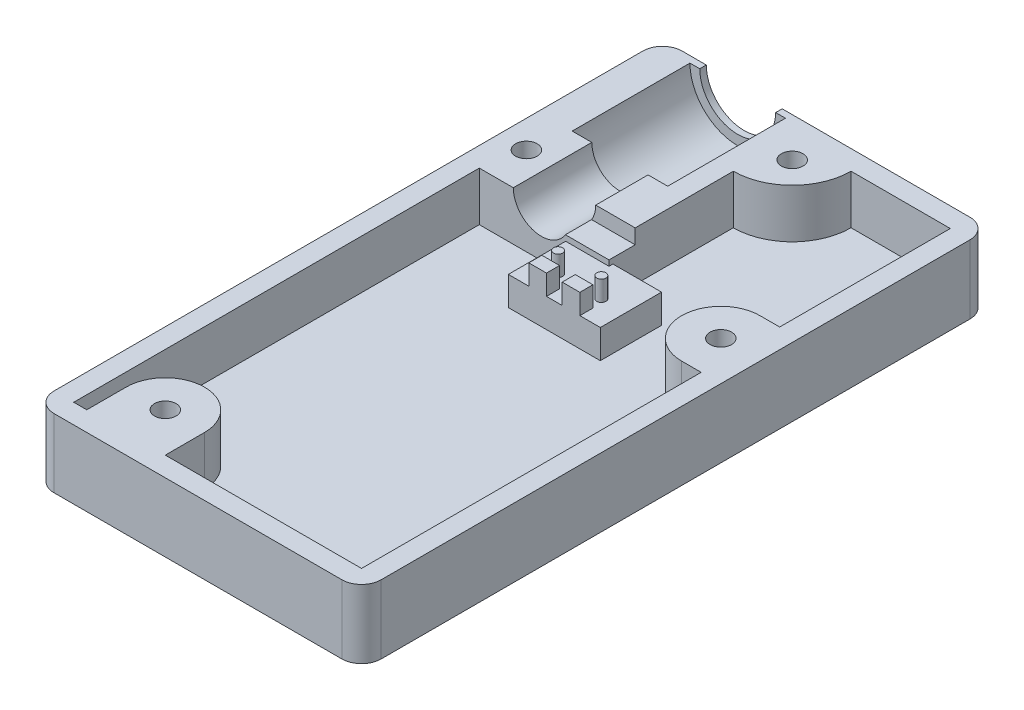
SolidWorks part; units mm, degrees
ref_plane "前视基准面" through (0, 0, 0) normal (0, 0, 1) x (1, 0, 0)
ref_plane "上视基准面" through (0, 0, 0) normal (0, 1, 0) x (1, 0, 0)
ref_plane "右视基准面" through (0, 0, 0) normal (1, 0, 0) x (0, 0, -1)
sketch "草图1" plane through (0, 0, 0) normal (0, 0, 1) x (1, 0, 0)
  line L1 (50, 38) -> (0, 38)
  line L2 (50, 38) -> (50, 0)
  line L3 (50, 0) -> (0, 0)
  line L4 (0, 38) -> (0, 0)
  dimension "D1" = 50
  dimension "D2" = 38
extrude "凸台-拉伸1" add sketch "草图1" against normal blind 3
sketch "草图2" plane through (0, 0, 0) normal (0, 0, 1) x (1, 0, 0)
  line L8 (50, 0) -> (50, 38)
  line L9 (50, 38) -> (0, 38)
  line L10 (0, 38) -> (0, 0)
  line L11 (0, 0) -> (50, 0)
  line L12 (50, 0) -> (50, 38)
  line L13 (50, 38) -> (0, 38)
  line L14 (0, 38) -> (0, 0)
  line L15 (0, 0) -> (50, 0)
  line L20 (47, 3) -> (47, 35)
  line L21 (47, 35) -> (3, 35)
  line L22 (3, 35) -> (3, 3)
  line L23 (3, 3) -> (47, 3)
  line L24 (47, 3) -> (47, 35)
  line L25 (47, 35) -> (3, 35)
  line L26 (3, 35) -> (3, 3)
  line L27 (3, 3) -> (47, 3)
  dimension "D1" = 0
  dimension "D2" = 3
extrude "凸台-拉伸2" add sketch "草图2" along normal blind 90
sketch "草图4" plane through (0, 0, -3) normal (0, 0, -1) x (-1, 0, 0)
  line L0 (-50, 38) -> (0, 38) construction
  line L1 (0, 38) -> (0, 0) construction
  circle A0 centre (-12.5, 10.5) radius 7.3
  dimension "D1" = 14.6
  dimension "D3" = 12.5
  dimension "D2" = 27.5
extrude "切除-拉伸1" cut sketch "草图4" against normal blind 45.2
sketch "草图5" plane through (0, 0, 0) normal (0, 0, 1) x (1, 0, 0)
  circle A0 centre (12.5, 10.5) radius 7.3
  circle A1 centre (12.5, 10.5) radius 7.3 construction
  circle A2 centre (12.5, 10.5) radius 10.3
  dimension "D1" = 3
extrude "凸台-拉伸3" add sketch "草图5" along normal blind 16
sketch "草图6" plane through (0, 0, -3) normal (0, 0, -1) x (-1, 0, 0)
  circle A0 centre (-12.5, 10.5) radius 5.8
  circle A3 centre (-12.5, 10.5) radius 7.3 construction
  circle A4 centre (-12.5, 10.5) radius 8.3
  circle A5 centre (-12.5, 10.5) radius 8.3
  dimension "D1" = 1
  dimension "D2" = 1.5
extrude "凸台-拉伸5" add sketch "草图6" against normal blind 1
sketch "草图7" plane through (0, 0, 16) normal (0, 0, 1) x (1, 0, 0)
  line L2 (5.4403, 3) -> (19.5597, 3)
  line L4 (5.4403, 3) -> (19.5597, 3)
  line L5 (3, 14.4799) -> (3, 6.5201)
  line L8 (3, 14.4799) -> (3, 6.5201)
  arc A1 (3, 6.5201) -> (5.4403, 3) centre (12.5, 10.5) ccw
  arc A2 (3, 6.5201) -> (5.4403, 3) centre (12.5, 10.5) ccw
  circle A3 centre (12.5, 10.5) radius 4.3
  arc A10 (19.5597, 3) -> (3, 14.4799) centre (12.5, 10.5) ccw
  arc A11 (19.5597, 3) -> (3, 14.4799) centre (12.5, 10.5) ccw
  dimension "D2" = 8.6
  dimension "D1" = 0
extrude "凸台-拉伸6" add sketch "草图7" along normal blind 2
sketch "草图8" plane through (0, 0, 18) normal (0, 0, 1) x (1, 0, 0)
  circle A1 centre (12.5, 10.5) radius 6.3
  circle A2 centre (12.5, 10.5) radius 4.3
  circle A3 centre (12.5, 10.5) radius 4.3
  dimension "D1" = 0
  dimension "D2" = 2
extrude "凸台-拉伸7" add sketch "草图8" along normal blind 10
sketch "草图9" plane through (0, 0, 28) normal (0, 0, 1) x (1, 0, 0)
  line L0 (8.2, 10.5) -> (16.8, 10.5) construction
  line L2 (16.1644, 8.25) -> (18.8, 8.25)
  line L3 (16.1644, 8.25) -> (16.1644, 12.75)
  line L4 (16.1644, 12.75) -> (18.8, 12.75)
  line L5 (18.8, 8.25) -> (18.8, 12.75)
  circle A0 centre (12.5, 10.5) radius 4.3 construction
  circle A1 centre (12.5, 10.5) radius 6.3 construction
  dimension "D1" = 4.5
extrude "切除-拉伸2" cut sketch "草图9" against normal blind 4
sketch "草图10" plane through (0, 3, 0) normal (0, 1, 0) x (1, 0, 0)
  line L0 (19.33, -36.76) -> (19.33, -34.76)
  line L1 (19.33, -34.76) -> (22.03, -34.76)
  line L2 (22.03, -34.76) -> (22.03, -36.76)
  line L3 (22.03, -36.76) -> (19.33, -36.76)
  line L8 (23.23, -37.46) -> (23.23, -28) construction
  line L9 (23.43, -37.46) -> (23.03, -37.46) construction
  line L10 (16.8, -28) -> (29.66, -28) construction
  line L11 (27.13, -34.76) -> (24.43, -34.76)
  line L12 (24.43, -34.76) -> (24.43, -36.76)
  line L13 (24.43, -36.76) -> (27.13, -36.76)
  line L14 (27.13, -36.76) -> (27.13, -34.76)
  line L15 (18.53, -37.26) -> (18.53, -34.14) construction
  line L16 (22.83, -37.26) -> (22.83, -34.14) construction
  line L17 (20.92, -34.36) -> (18.92, -34.36) construction
  circle A0 centre (19.92, -32.88) radius 0.7
  circle A1 centre (26.54, -32.88) radius 0.7
  circle A2 centre (19.92, -32.88) radius 0.98 construction
  point P14 (18.53, -35.7)
  dimension "D1" = 1.4
  dimension "D2" = 0.28
  dimension "D3" = 0.8
  dimension "D4" = 0.8
  dimension "D5" = 0.4
  dimension "D6" = 2
extrude "凸台-拉伸8" add sketch "草图10" along normal blind 32
sketch "草图11" plane through (0, 3, 0) normal (0, 1, 0) x (1, 0, 0)
  line L0 (16.8, -34.14) -> (16.8, -28) construction
  line L1 (16.2, -36.76) -> (30.26, -36.76)
  line L2 (16.2, -36.76) -> (16.2, -27.4)
  line L3 (16.2, -27.4) -> (30.26, -27.4)
  line L4 (30.26, -36.76) -> (30.26, -27.4)
  line L5 (29.66, -28) -> (29.66, -34.14) construction
  line L6 (19.33, -36.76) -> (22.03, -36.76) construction
  line L7 (16.8, -28) -> (29.66, -28) construction
  dimension "D1" = 0.6
  dimension "D2" = 0.6
  dimension "D3" = 0.6
extrude "凸台-拉伸9" add sketch "草图11" along normal blind 4.4
sketch "草图12" plane through (0, 35, 0) normal (0, -1, 0) x (1, 0, 0)
  line L1 (16.2, 27.4) -> (30.26, 27.4)
  line L2 (16.2, 27.4) -> (16.2, 36.76)
  line L3 (16.2, 36.76) -> (30.26, 36.76)
  line L4 (30.26, 27.4) -> (30.26, 36.76)
extrude "凸台-拉伸10" add sketch "草图12" along normal blind 21.2
sketch "草图13" plane through (0, 38, 0) normal (0, 1, 0) x (1, 0, 0)
  line L0 (12.3, -64.096) -> (42.5, -64.096) construction
  line L1 (40.04, -72.896) -> (39.0237, -72.896) construction
  line L2 (38.625, -74.196) -> (44.4, -74.196)
  line L3 (45.4, -73.196) -> (45.4, -54.996)
  line L4 (44.4, -57.796) -> (44.4, -70.396) construction
  line L5 (38.625, -53.996) -> (44.4, -53.996)
  circle A0 centre (27.4, -64.096) radius 15.1 construction
  circle A1 centre (27.4, -64.096) radius 14.1 construction
  arc A2 (38.625, -74.196) -> (38.625, -53.996) centre (27.4, -64.096) cw
  arc A3 (44.4, -53.996) -> (45.4, -54.996) centre (44.4, -54.996) cw
  arc A4 (44.4, -74.196) -> (45.4, -73.196) centre (44.4, -73.196) ccw
  point P16 (45.4, -64.096)
  point P18 (45.4, -53.996)
  point P21 (45.4, -74.196)
  dimension "D1" = 1
  dimension "D2" = 1.3
  dimension "D4" = 1
  dimension "D3" = 1
extrude "切除-拉伸3" cut sketch "草图13" against normal blind 3
sketch "草图14" plane through (0, 35, 0) normal (0, -1, 0) x (1, 0, 0)
  line L0 (14.3, 64.096) -> (40.5, 64.096) construction
  line L1 (23.9, 46.596) -> (23.9, 50.4373) construction
  line L2 (30.9, 46.596) -> (30.9, 50.4373) construction
  line L3 (23.9, 46.596) -> (23.9, 49.4072)
  line L4 (30.9, 46.596) -> (30.9, 49.4072)
  line L5 (30.9, 81.596) -> (30.9, 78.7847)
  line L6 (23.9, 81.596) -> (23.9, 78.7847)
  circle A0 centre (27.4, 46.596) radius 1.65
  circle A1 centre (27.4, 64.096) radius 13.1 construction
  arc A2 (23.9, 49.4072) -> (30.9, 49.4072) centre (27.4, 64.096) ccw
  arc A3 (38.625, 74.196) -> (38.625, 53.996) centre (27.4, 64.096) ccw construction
  arc A4 (23.9, 46.596) -> (30.9, 46.596) centre (27.4, 46.596) ccw
  arc A5 (23.9, 46.596) -> (30.9, 46.596) centre (27.4, 46.596) ccw construction
  arc A6 (23.9, 81.596) -> (30.9, 81.596) centre (27.4, 81.596) cw
  arc A7 (23.9, 78.7847) -> (30.9, 78.7847) centre (27.4, 64.096) cw
  circle A8 centre (27.4, 81.596) radius 1.65
  dimension "D1" = 3.3
extrude "凸台-拉伸11" add sketch "草图14" along normal blind 15.5
sketch "草图15" plane through (0, 35, 0) normal (0, -1, 0) x (1, 0, 0)
  line L0 (23.9, 46.596) -> (23.9, 50.4373) construction
  line L1 (20.4, 50.7165) -> (20.4, 46.596)
  line L2 (27.4, 48.696) -> (27.4, 44.496) construction
  line L4 (34.4, 50.7165) -> (34.4, 46.596)
  line L5 (45.4, 64.096) -> (12.3, 64.096) construction
  line L6 (45.4, 73.196) -> (45.4, 54.996) construction
  line L7 (20.4, 77.4754) -> (20.4, 81.596)
  line L8 (34.4, 77.4754) -> (34.4, 81.596)
  circle A0 centre (27.4, 46.596) radius 1.65
  circle A1 centre (27.4, 46.596) radius 2.1 construction
  arc A2 (20.4, 46.596) -> (34.4, 46.596) centre (27.4, 46.596) ccw
  arc A3 (20.4, 50.7165) -> (34.4, 50.7165) centre (27.4, 64.096) ccw
  arc A4 (23.9, 78.7847) -> (23.9, 49.4072) centre (27.4, 64.096) ccw construction
  arc A5 (20.4, 77.4754) -> (34.4, 77.4754) centre (27.4, 64.096) cw
  circle A6 centre (27.4, 81.596) radius 1.65
  arc A7 (20.4, 81.596) -> (34.4, 81.596) centre (27.4, 81.596) cw
  arc A9 (30.9, 49.4072) -> (38.625, 53.996) centre (27.4, 64.096) ccw construction
  line M14 (23.9, 78.7847) -> (23.9, 81.596)
  arc M15 (23.9, 81.596) -> (30.9, 81.596) centre (27.4, 81.596) cw
  line M16 (30.9, 81.596) -> (30.9, 78.7847)
  line M24 (30.9, 49.4072) -> (30.9, 46.596)
  arc M25 (30.9, 46.596) -> (23.9, 46.596) centre (27.4, 46.596) cw
  line M26 (23.9, 46.596) -> (23.9, 49.4072)
  dimension "D1" = 3.3
  dimension "D2" = 7
extrude "凸台-拉伸12" add sketch "草图15" along normal blind 15.5 contours L1 A2 L4 M24 M25 M26 | A7 L7 L8 M14 M15 M16 region at (22.0467, 35, 49.7857) region at (20.5788, 35, 79.5357)
sketch "草图16" plane through (0, 19.5, 0) normal (0, -1, 0) x (1, 0, 0)
  line L0 (45.4, 64.096) -> (12.3, 64.096) construction
  line L1 (45.4, 73.196) -> (45.4, 54.996) construction
  line L24 (31.3, 81.596) -> (31.3, 77.2291)
  line L25 (23.5, 77.2291) -> (23.5, 81.596)
  line L26 (31.3, 46.596) -> (31.3, 50.9628)
  line L27 (23.5, 50.9628) -> (23.5, 46.596)
  line L28 (31.3, 46.596) -> (31.3, 50.9628)
  line L29 (23.5, 50.9628) -> (23.5, 46.596)
  arc A0 (20.4, 77.4754) -> (20.4, 50.7165) centre (27.4, 64.096) ccw construction
  arc A25 (23.5, 81.596) -> (31.3, 81.596) centre (27.4, 81.596) cw
  arc A26 (23.5, 77.2291) -> (31.3, 77.2291) centre (27.4, 64.096) cw
  arc A27 (23.5, 50.9628) -> (31.3, 50.9628) centre (27.4, 64.096) ccw
  arc A28 (23.5, 46.596) -> (31.3, 46.596) centre (27.4, 46.596) ccw
  arc A29 (23.5, 50.9628) -> (31.3, 50.9628) centre (27.4, 64.096) ccw
  arc A30 (23.5, 46.596) -> (31.3, 46.596) centre (27.4, 46.596) ccw
  dimension "D1" = 0.4
extrude "切除-拉伸4" cut sketch "草图16" against normal blind 0.8
sketch "草图17" plane through (0, 0, 0) normal (0, 0, 1) x (1, 0, 0)
  line L1 (3, 3) -> (47, 3) construction
  line L2 (22.83, 10.5392) -> (22.83, 3)
  line L3 (22.83, 10.2892) -> (22.83, 10.7892) construction
  line L4 (22.83, 3) -> (19.5597, 3)
  line L5 (5.4403, 3) -> (3, 3)
  line L6 (3, 3) -> (3, 6.5201)
  line L7 (3, 14.4799) -> (3, 35)
  line L8 (3, 35) -> (22.83, 35)
  line L9 (47, 35) -> (3, 35) construction
  line L10 (22.83, 10.5392) -> (22.83, 35)
  arc A1 (5.4403, 3) -> (3, 6.5201) centre (12.5, 10.5) cw
  arc A2 (3, 6.5201) -> (5.4403, 3) centre (12.5, 10.5) ccw construction
  arc A3 (3, 14.4799) -> (19.5597, 3) centre (12.5, 10.5) cw
  arc M1 (3, 14.4799) -> (19.5597, 3) centre (12.5, 10.5) cw
  line M2 (19.5597, 3) -> (47, 3)
  line M4 (47, 35) -> (3, 35)
  line M5 (3, 35) -> (3, 14.4799)
extrude "凸台-拉伸13" add sketch "草图17" along normal blind 18 contours L2 L10 M4 M5 M1 M2 | L5 A1 L6 region at (13.2696, 26.2496, 0) region at (3.7547, 4.0789, 0)
sketch "草图18" plane through (0, 0, 18) normal (0, 0, 1) x (1, 0, 0)
  line L8 (3, 35) -> (3, 3)
  line L9 (3, 3) -> (22.83, 3)
  line L10 (22.83, 3) -> (22.83, 35)
  line L11 (22.83, 35) -> (3, 35)
  line L12 (3, 35) -> (3, 3)
  line L13 (3, 3) -> (22.83, 3)
  line L14 (22.83, 3) -> (22.83, 35)
  line L15 (22.83, 35) -> (3, 35)
  circle A0 centre (12.5, 10.5) radius 6.3
  circle A1 centre (12.5, 10.5) radius 6.3 construction
  dimension "D1" = 0
extrude "凸台-拉伸14" add sketch "草图18" along normal blind 10
sketch "草图19" plane through (0, 0, 28) normal (0, 0, 1) x (1, 0, 0)
  line L0 (18.3845, 8.25) -> (22.83, 8.25)
  line L1 (22.83, 7.4) -> (22.83, 13.8) construction
  line L2 (22.83, 8.25) -> (22.83, 12.75)
  line L3 (22.83, 12.75) -> (18.3845, 12.75)
  line L4 (18.3845, 12.75) -> (16.1644, 12.75) construction
  line L5 (18.3845, 8.25) -> (18.3845, 12.75)
extrude "切除-拉伸5" cut sketch "草图19" against normal blind 4
sketch "草图23" plane through (0, 35, 0) normal (0, -1, 0) x (1, 0, 0)
  line L0 (22.83, 27.4) -> (22.83, 0) construction
  line L1 (22.83, 0) -> (47, 0) construction
  line L2 (22.83, 0) -> (22.83, 9)
  line L3 (22.83, 0) -> (31.83, 0)
  line L4 (47, 90) -> (47, 0) construction
  line L5 (44, 26.08) -> (47, 26.08)
  line L6 (47, 26.08) -> (47, 38.08)
  line L7 (45.65, 32.08) -> (42.35, 32.08) construction
  line L8 (44, 38.08) -> (47, 38.08)
  line L9 (30.26, 32.08) -> (42.35, 32.08) construction
  line L10 (30.26, 36.76) -> (30.26, 27.4) construction
  line L11 (3, 90) -> (3, 28) construction
  line L12 (0, 90) -> (50, 90) construction
  line L13 (11, 82.35) -> (11, 85.65) construction
  line L14 (5, 90) -> (5, 84)
  line L15 (17, 90) -> (17, 84)
  line L16 (5, 90) -> (17, 90)
  circle A0 centre (25.83, 3) radius 1.65
  arc A1 (31.83, 0) -> (22.83, 9) centre (22.83, 0) ccw
  circle A2 centre (44, 32.08) radius 1.65
  arc A3 (44, 26.08) -> (44, 38.08) centre (44, 32.08) cw
  circle A4 centre (11, 84) radius 1.65
  arc A5 (5, 84) -> (17, 84) centre (11, 84) ccw
  point P22 (47, 32.08)
  dimension "D1" = 3
  dimension "D4" = 3.3
  dimension "D5" = 3
  dimension "D6" = 3.3
  dimension "D7" = 6
  dimension "D8" = 3.3
  dimension "D9" = 8
  dimension "D10" = 6
  dimension "D11" = 6
  dimension "D2" = 3
  dimension "D3" = 9
extrude "凸台-拉伸16" add sketch "草图23" along normal through all
sketch "草图25" plane through (0, 35, 0) normal (0, -1, 0) x (1, 0, 0)
  line L0 (0, -3) -> (0, 90) construction
  line L1 (16.2, 28) -> (3, 28) construction
  circle A0 centre (4.2, 22) radius 1.65
  circle A1 centre (4.2, 22) radius 3 construction
  circle A2 centre (25.83, 3) radius 1.65
  circle A7 centre (44, 32.08) radius 1.65
  circle A8 centre (44, 32.08) radius 1.65
  circle A10 centre (11, 84) radius 1.65
  circle A11 centre (11, 84) radius 1.65
  dimension "D1" = 3.3
  dimension "D2" = 6
  dimension "D3" = 4.2
  dimension "D4" = 6
  dimension "D5" = 0
  dimension "D6" = 0
extrude "切除-拉伸7" cut sketch "草图25" against normal through all and the other way through all
sketch "草图26" plane through (0, 38, 0) normal (0, 1, 0) x (1, 0, 0)
  line L0 (0, 3) -> (0, -90) construction
  line L1 (4.2, -18.5371) -> (1.201, -20.2685)
  line L2 (1.201, -20.2685) -> (1.201, -23.7315)
  line L3 (1.201, -23.7315) -> (4.2, -25.4629)
  line L4 (4.2, -25.4629) -> (7.199, -23.7315)
  line L5 (7.199, -23.7315) -> (7.199, -20.2685)
  line L6 (7.199, -20.2685) -> (4.2, -18.5371)
  line L7 (25.83, -6.4629) -> (28.829, -4.7315)
  line L8 (28.829, -4.7315) -> (28.829, -1.2685)
  line L9 (28.829, -1.2685) -> (25.83, 0.4629)
  line L10 (25.83, 0.4629) -> (22.831, -1.2685)
  line L11 (22.831, -1.2685) -> (22.831, -4.7315)
  line L12 (22.831, -4.7315) -> (25.83, -6.4629)
  line L14 (11, -80.5371) -> (8.001, -82.2685)
  line L15 (8.001, -82.2685) -> (8.001, -85.7315)
  line L16 (8.001, -85.7315) -> (11, -87.4629)
  line L17 (11, -87.4629) -> (13.999, -85.7315)
  line L18 (13.999, -85.7315) -> (13.999, -82.2685)
  line L19 (13.999, -82.2685) -> (11, -80.5371)
  line L20 (44, -28.6171) -> (41.001, -30.3485)
  line L21 (41.001, -30.3485) -> (41.001, -33.8115)
  line L22 (41.001, -33.8115) -> (44, -35.5429)
  line L23 (44, -35.5429) -> (46.999, -33.8115)
  line L24 (46.999, -33.8115) -> (46.999, -30.3485)
  line L25 (46.999, -30.3485) -> (44, -28.6171)
  circle A0 centre (4.2, -22) radius 2.999 construction
  circle A1 centre (25.83, -3) radius 2.999 construction
  circle A2 centre (11, -84) radius 2.999 construction
  circle A3 centre (44, -32.08) radius 2.999 construction
  dimension "D1" = 5.998
extrude "切除-拉伸8" cut sketch "草图26" against normal blind 24.5
sketch "草图29" plane through (0, 0, 90) normal (0, 0, 1) x (1, 0, 0)
  line L8 (0, 0) -> (50, 0)
  line L9 (50, 0) -> (50, 38)
  line L10 (50, 38) -> (0, 38)
  line L11 (0, 38) -> (0, 0)
  line L12 (0, 0) -> (50, 0)
  line L13 (50, 0) -> (50, 38)
  line L14 (50, 38) -> (0, 38)
  line L15 (0, 38) -> (0, 0)
  dimension "D1" = 0
extrude "凸台-拉伸17" add sketch "草图29" along normal blind 3
fillet "圆角1" radius 3 4 edges at (50, 19, 93) (50, 19, -3) (0, 19, 93) (0, 19, -3)
ref_plane "基准面3" through (0, 10.5, 0) normal (0, 1, 0) x (1, 0, 0)
sketch "草图30" plane through (50, 0, 0) normal (1, 0, 0) x (0, 0, -1)
  line L0 (-93, 0) -> (-93, 38) construction
  line L1 (-93, 10.51) -> (3, 10.51)
  line L2 (-93, 10.51) -> (-93, 10.49)
  line L3 (-93, 10.49) -> (3, 10.49)
  line L4 (3, 10.51) -> (3, 10.49)
  line L5 (3, 38) -> (3, 0) construction
  line L6 (27.5, 10.5) -> (-27.5, 10.5) construction
  dimension "D1" = 0.01
  dimension "D2" = 0.01
extrude "切除-拉伸9" cut sketch "草图30" against normal through all
delete or keep bodies "实体-删除/保留 2" type keep bodies bodies 132
sketch "草图31" plane through (0, 0, 0) normal (0, -1, 0) x (1, 0, 0)
  circle A0 centre (4.2, 22) radius 3
  circle A1 centre (25.83, 3) radius 3
  circle A2 centre (11, 84) radius 3
  circle A3 centre (44, 32.08) radius 3
  dimension "D1" = 6
extrude "切除-拉伸10" cut sketch "草图31" against normal blind 2
